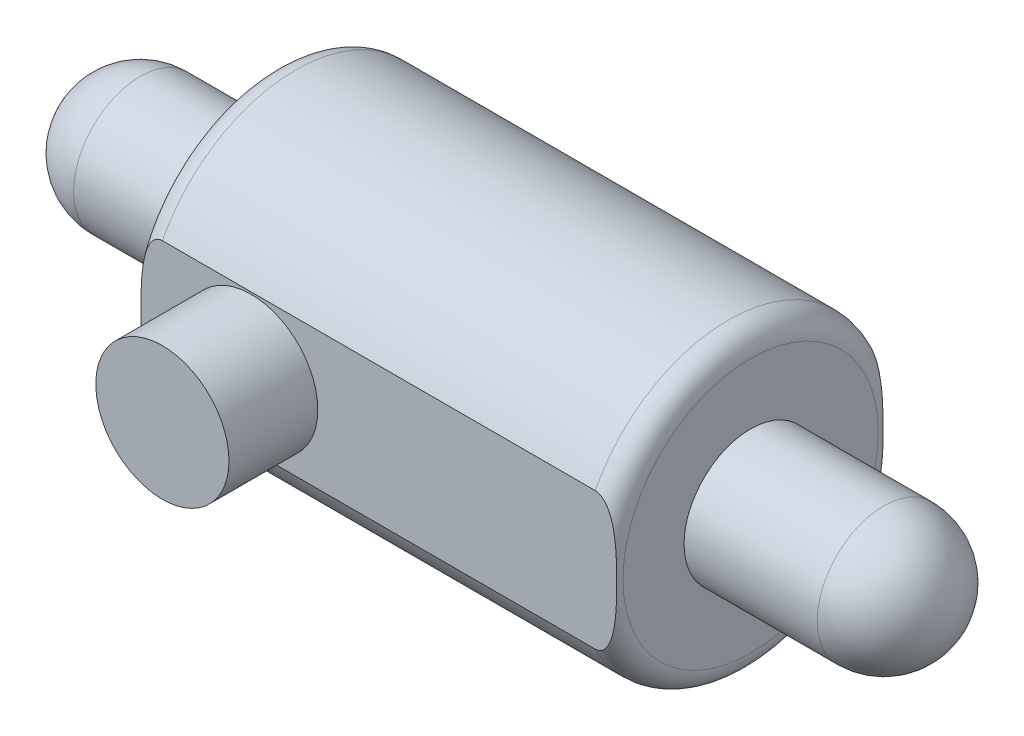
SolidWorks part; units mm, degrees
ref_plane "Front Plane" through (0, 0, 0) normal (0, 0, 1) x (1, 0, 0)
ref_plane "Top Plane" through (0, 0, 0) normal (0, 1, 0) x (1, 0, 0)
ref_plane "Right Plane" through (0, 0, 0) normal (1, 0, 0) x (0, 0, -1)
sketch "Sketch1" plane through (0, 0, 0) normal (0, 1, 0) x (1, 0, 0)
  line L1 (-47.3109, 0) -> (-4.3109, 0)
  line L2 (-47.3109, 0) -> (-47.3109, -13.5)
  line L3 (-47.3109, -13.5) -> (-4.3109, -13.5)
  line L4 (-4.3109, 0) -> (-4.3109, -13.5)
revolve "Revolve1" add sketch "Sketch1" angle 360 about L1
sketch "Sketch4" plane through (0, 0, 0) normal (0, 0, 1) x (1, 0, 0)
  line L0 (-47.3109, 13.5) -> (-47.3109, -13.5) construction
  line L1 (-4.3109, 13.5) -> (-47.3109, 13.5) construction
  circle A0 centre (-37.3109, 0) radius 6
  dimension "D1" = 12
  dimension "D2" = 10
  dimension "D3" = 13.5
extrude "Boss-Extrude2" add sketch "Sketch4" along normal blind 20
sketch "Sketch5" plane through (-47.3109, 0, 0) normal (-1, 0, 0) x (0, 0, 1)
  circle A1 centre (0, 0) radius 6
  dimension "D1" = 12
extrude "Boss-Extrude3" add sketch "Sketch5" along normal blind 18
fillet "Fillet1" radius 6 1 edges at (-65.3109, 0, 6)
sketch "Sketch6" plane through (-4.3109, 0, 0) normal (1, 0, 0) x (0, 0, -1)
  circle A0 centre (0, 0) radius 6
  dimension "D1" = 12
extrude "Boss-Extrude4" add sketch "Sketch6" along normal blind 18
fillet "Fillet2" radius 6 1 edges at (13.6891, 0, -6)
fillet "Fillet3" radius 2 2 edges at (-4.3109, 0, 13.5) (-47.3109, 0, 13.5)
ref_axis "Axis1" through (-6.3109, 0, 0) along (-1, 0, 0)
ref_point "Point1"
ref_plane "Plane1" through (0, 0, -12) normal (0, 0, 1) x (1, 0, 0)
sketch "Sketch8" plane through (0, 0, -12) normal (0, 0, 1) x (1, 0, 0)
  line L4 (-4.3109, 11.5) -> (-47.3109, 11.5)
  line L5 (-4.3109, 11.5) -> (-4.3109, -11.5)
  line L6 (-4.3109, -11.5) -> (-47.3109, -11.5)
  line L7 (-47.3109, 11.5) -> (-47.3109, -11.5)
  arc A1 (-4.3109, 11.5) -> (-6.3109, 13.5) centre (-6.3109, 11.5) ccw construction
extrude "Cut-Extrude2" cut sketch "Sketch8" against normal blind 7
ref_plane "Plane2" through (0, 0, 12) normal (0, 0, 1) x (1, 0, 0)
sketch "Sketch9" plane through (0, 0, 12) normal (0, 0, 1) x (1, 0, 0)
  line L0 (-4.3109, -11.5) -> (-4.3109, 11.5) construction
  line L1 (-47.3109, 11.5) -> (-4.3109, 11.5)
  line L2 (-47.3109, 11.5) -> (-47.3109, -11.5)
  line L3 (-47.3109, -11.5) -> (-4.3109, -11.5)
  line L4 (-4.3109, 11.5) -> (-4.3109, -11.5)
  arc A0 (-6.3109, -13.5) -> (-4.3109, -11.5) centre (-6.3109, -11.5) ccw construction
  circle A1 centre (-37.3109, 0) radius 6
extrude "Cut-Extrude3" cut sketch "Sketch9" along normal blind 5
